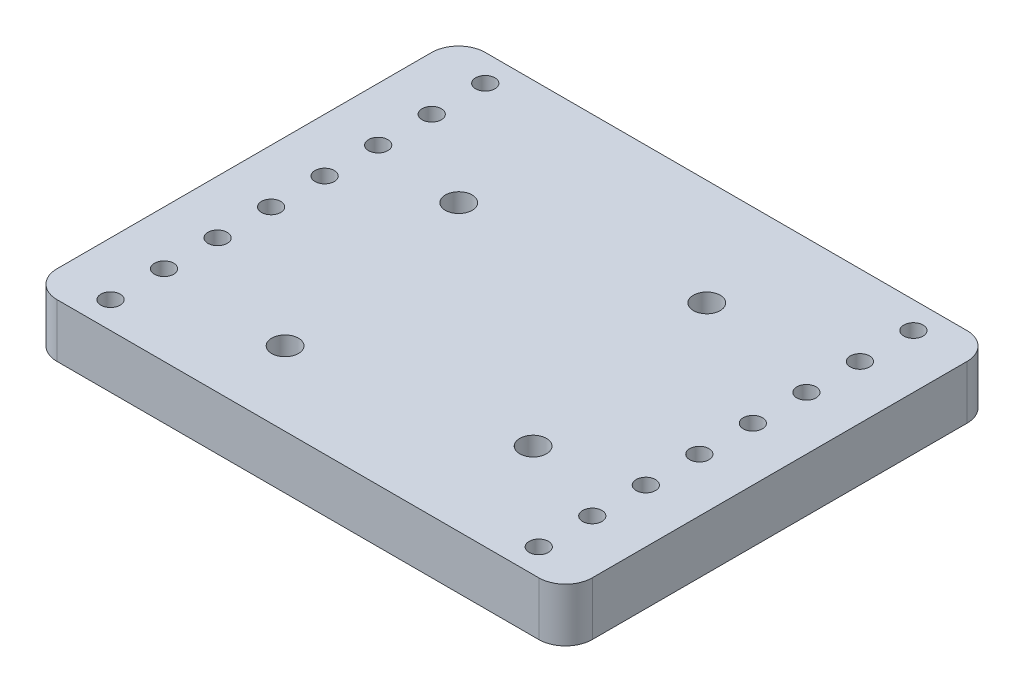
SolidWorks part; units mm, degrees
ref_plane "Front Plane" through (0, 0, 0) normal (0, 0, 1) x (1, 0, 0)
ref_plane "Top Plane" through (0, 0, 0) normal (0, 1, 0) x (1, 0, 0)
ref_plane "Right Plane" through (0, 0, 0) normal (1, 0, 0) x (0, 0, -1)
sketch "Sketch1" plane through (0, 0, 0) normal (0, 1, 0) x (1, 0, 0)
  line L1 (-63.5, -50.8) -> (63.5, -50.8)
  line L2 (-63.5, -50.8) -> (-63.5, 50.8)
  line L3 (-63.5, 50.8) -> (63.5, 50.8)
  line L4 (63.5, -50.8) -> (63.5, 50.8)
  line L5 (-63.5, -50.8) -> (63.5, 50.8) construction
  line L6 (-63.5, 50.8) -> (63.5, -50.8) construction
  point P0 (0, 0)
  dimension "D1" = 101.6
  dimension "D2" = 127
extrude "Initial Plate" add sketch "Sketch1" along normal blind 12.7
sketch "Sketch2" plane through (0, 12.7, 0) normal (0, 1, 0) x (1, 0, 0)
  line L0 (25.0141, 0.6007) -> (-25.0141, -8.2207) construction
  line L1 (-20.6035, -33.2348) -> (-29.4248, 16.7935) construction
  line L2 (29.4248, -24.4135) -> (20.6035, 25.6148) construction
  line L3 (-63.5, -50.8) -> (63.5, -50.8) construction
  line L4 (-27.6706, 10.6548) -> (-38.122, 8.8119) construction
  line L5 (-21.0546, -26.8664) -> (-31.506, -28.7092) construction
  line L6 (0, 50.8) -> (0, -50.8) construction
  line L7 (63.5, 50.8) -> (-63.5, 50.8) construction
  circle A0 centre (-29.4248, 16.7935) radius 3.175
  circle A1 centre (-20.6035, -33.2348) radius 3.175
  circle A2 centre (29.4248, -24.4135) radius 3.175
  circle A3 centre (20.6035, 25.6148) radius 3.175
  circle A4 centre (-29.4248, 16.7935) radius 6.35 construction
  circle A5 centre (-20.6035, -33.2348) radius 6.35 construction
  point P4 (0, 0)
  point P7 (-25.0141, -8.2207)
  point P10 (25.0141, 0.6007)
  point P26 (0, 0)
  point P27 (0, -3.81)
  dimension "D5" = 6.35
  dimension "D3" = 12.7
  dimension "D6" = 38.1
  dimension "D1" = 50.8
  dimension "D2" = 90
  dimension "D4" = 10
  dimension "D7" = 3.81
extrude "Bearing Stack Holes" cut sketch "Sketch2" against normal through all
sketch "Sketch3" plane through (0, 12.7, 0) normal (0, 1, 0) x (1, 0, 0)
  line L0 (50.8, -44.45) -> (-50.8, -44.45) construction
  line L1 (0, 0) -> (0, -44.45) construction
  line L2 (-63.5, -50.8) -> (63.5, -50.8) construction
  line L3 (-63.5, 50.8) -> (-63.5, -50.8) construction
  circle A0 centre (-50.8, -44.45) radius 2.286
  circle A1 centre (50.8, -44.45) radius 2.286
  point P4 (0, 0)
  dimension "D1" = 4.572
  dimension "D2" = 6.35
  dimension "D3" = 12.7
extrude "Initial Mounting Hole" cut sketch "Sketch3" against normal through all
pattern_linear "Mounting Pattern" count 8 spacing 12.7 along (0, 0, -1) of "Initial Mounting Hole"
fillet "Fillet1" radius 6.35 4 edges at (63.5, 6.35, -50.8) (63.5, 6.35, 50.8) (-63.5, 6.35, 50.8) (-63.5, 6.35, -50.8)
